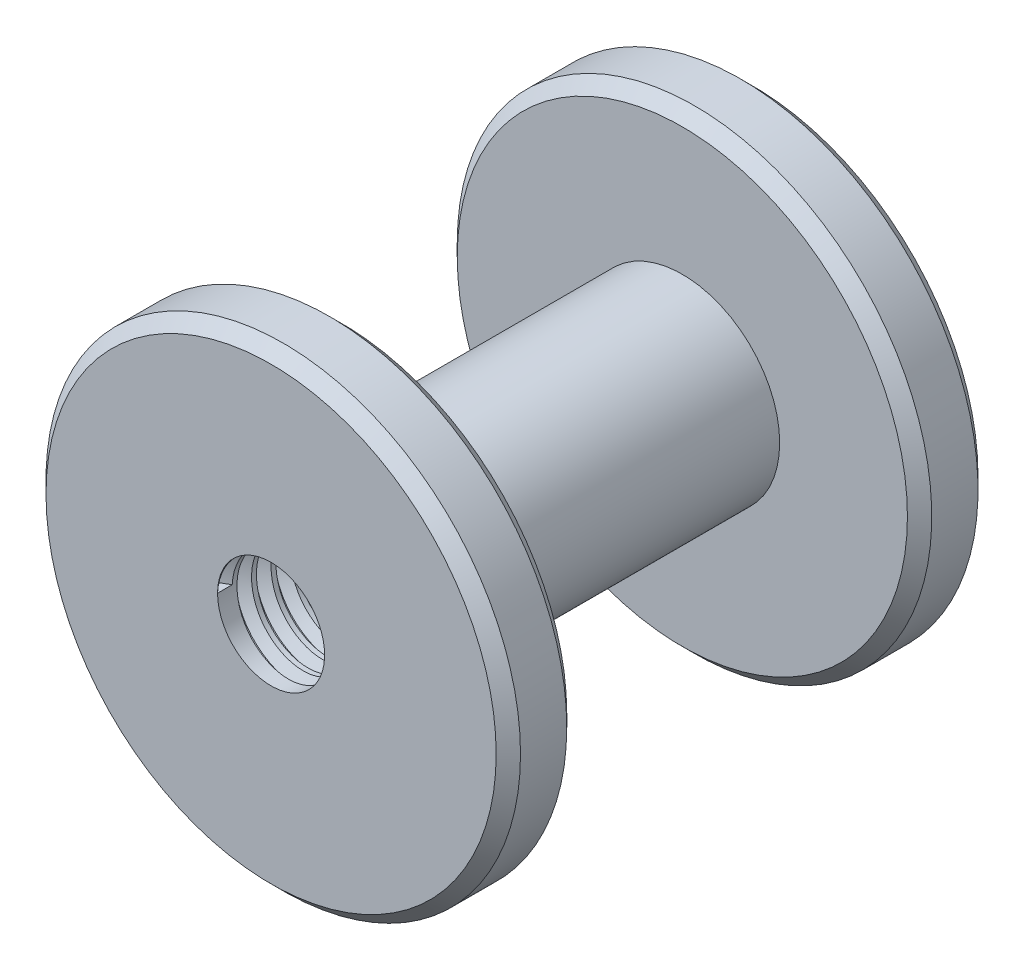
SolidWorks part; units mm, degrees
ref_plane "Ebene vorne" through (0, 0, 0) normal (0, 0, 1) x (1, 0, 0)
ref_plane "Ebene oben" through (0, 0, 0) normal (0, 1, 0) x (1, 0, 0)
ref_plane "Ebene rechts" through (0, 0, 0) normal (1, 0, 0) x (0, 0, -1)
sketch "Skizze1" plane through (0, 0, 0) normal (0, 0, 1) x (1, 0, 0)
  circle A0 centre (0, 0) radius 4
  dimension "D1" = 8
extrude "Aufsatz-Linear austragen1" add sketch "Skizze1" along normal mid plane 17.8
sketch "Skizze4" plane through (0, 0, 8.9) normal (0, 0, 1) x (1, 0, 0)
  circle A0 centre (0, 0) radius 1
  circle A1 centre (0, 0) radius 1.25
  dimension "D1" = 2.5
  dimension "D2" = 2
extrude "Schnitt-Linear austragen2" cut sketch "Skizze4" against normal blind 2
sketch "Skizze8" plane through (0, 0, -8.9) normal (0, 0, -1) x (-1, 0, 0)
  circle A0 centre (0, 0) radius 5
  dimension "D1" = 10
extrude "Aufsatz-Linear austragen2" add sketch "Skizze8" along normal blind 1 contours A0
sketch "Skizze10" plane through (0, 0, 8.9) normal (0, 0, 1) x (1, 0, 0)
  circle A0 centre (0, 0) radius 4
  dimension "D1" = 8
extrude "Aufsatz-Linear austragen3" add sketch "Skizze10" along normal blind 1 and the other way blind 10 contours A0
sketch "Skizze12" plane through (0, 0, 9.9) normal (0, 0, 1) x (1, 0, 0)
  circle A0 centre (0, 0) radius 9.75
  dimension "D1" = 19.5
extrude "Aufsatz-Linear austragen4" add sketch "Skizze12" against normal blind 2.9
sketch "Skizze13" plane through (0, 0, -9.9) normal (0, 0, -1) x (-1, 0, 0)
  circle A0 centre (0, 0) radius 9.75
  dimension "D1" = 19.5
extrude "Aufsatz-Linear austragen5" add sketch "Skizze13" against normal blind 2.9
sketch "Skizze11" plane through (0, 0, 9.9) normal (0, 0, 1) x (1, 0, 0)
  circle A0 centre (0, 0) radius 2.25
  dimension "D1" = 4.5
sketch "Skizze14" plane through (0, 0, -9.9) normal (0, 0, -1) x (-1, 0, 0)
  circle A0 centre (0, 0) radius 2.2
  dimension "D1" = 4.4
extrude "Schnitt-Linear austragen4" cut sketch "Skizze14" against normal through all
thread "Gewinde1" pitch 0.8 method cut profile "Gewindeprofil1" start angle 0, offset 0, length 9, pitch 0.8, diameter 4.4
ref_plane "Ebene4" through (-2.2, 0, 9.9) normal (0, -1, 0) x (-1, 0, 0)
sketch "Gewindeprofil1" plane through (-2.2, 0, 9.9) normal (0, -1, 0) x (-1, 0, 0)
  line L0 (0, 0) -> (0, 0.8) construction
  line L1 (0, 0) -> (0.433, 0.25)
  line L2 (0.433, 0.25) -> (0.433, 0.35)
  line L3 (0.433, 0.35) -> (0, 0.6)
  line L4 (0.433, 0.3) -> (0, 0.3) construction
  line L11 (0, 0) -> (0, 0.6)
  point P2 (0, 0)
  dimension "Pitch" = 0.8
  dimension "Profile_Angle" = 60
  dimension "Profile_Land" = 0.1
  dimension "Profile_Height" = 0.433
thread "Gewinde2" pitch 0.8 method cut profile "Gewindeprofil2" start angle 0, offset 0, length 9, pitch 0.8, diameter 4.4
ref_plane "Ebene5" through (2.2, 0, -9.9) normal (0, -1, 0) x (1, 0, 0)
sketch "Gewindeprofil2" plane through (2.2, 0, -9.9) normal (0, -1, 0) x (1, 0, 0)
  line L0 (0, 0) -> (0, 0.8) construction
  line L1 (0, 0) -> (0.433, 0.25)
  line L2 (0.433, 0.25) -> (0.433, 0.35)
  line L3 (0.433, 0.35) -> (0, 0.6)
  line L4 (0.433, 0.3) -> (0, 0.3) construction
  line L11 (0, 0) -> (0, 0.6)
  point P2 (0, 0)
  dimension "Pitch" = 0.8
  dimension "Profile_Angle" = 60
  dimension "Profile_Land" = 0.1
  dimension "Profile_Height" = 0.433
chamfer "Fase1" distance 0.5 angle 45 4 edges at (-9.75, 0, -7) (9.75, 0, 7) (9.75, 0, 9.9) (-9.75, 0, -9.9)
